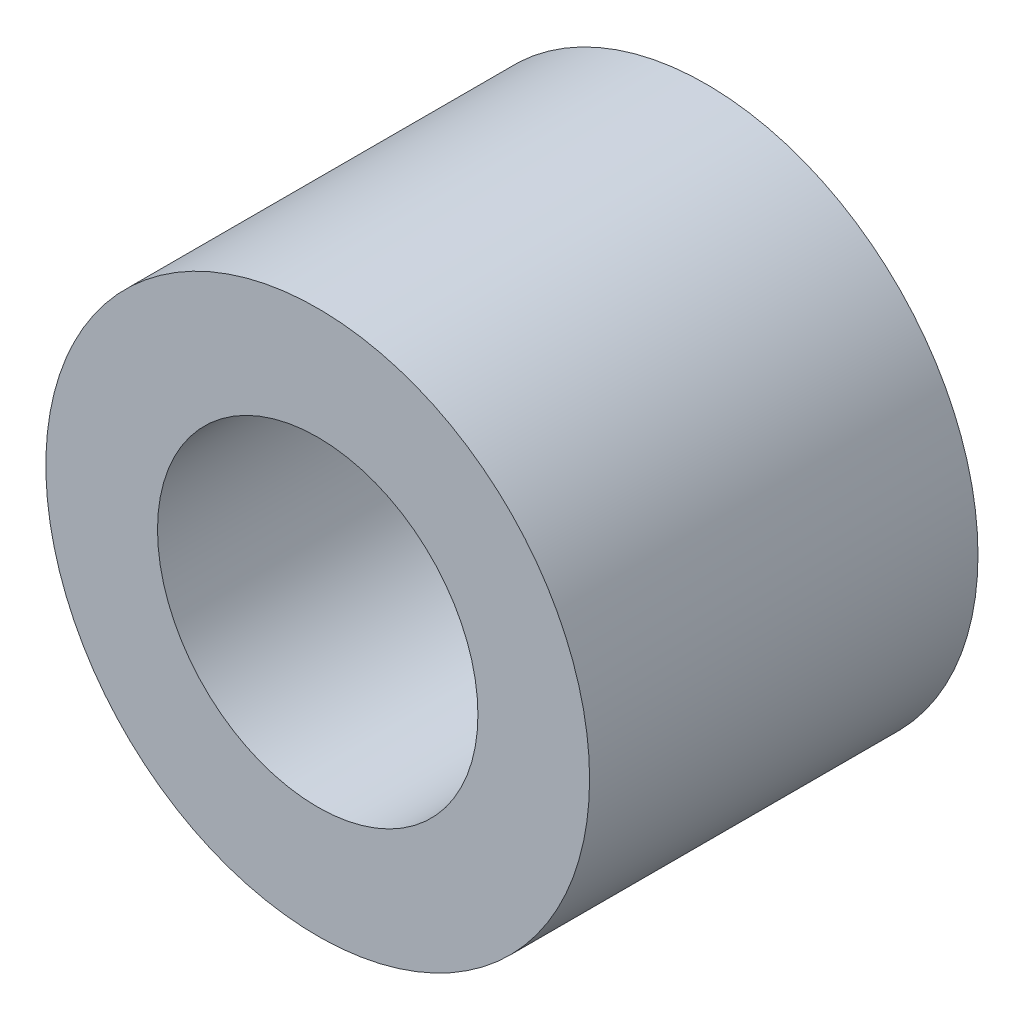
SolidWorks part; units mm, degrees
ref_plane "前视基准面" through (0, 0, 0) normal (0, 0, 1) x (1, 0, 0)
ref_plane "上视基准面" through (0, 0, 0) normal (0, 1, 0) x (1, 0, 0)
ref_plane "右视基准面" through (0, 0, 0) normal (1, 0, 0) x (0, 0, -1)
sketch "草图1" plane through (0, 0, 0) normal (0, 0, 1) x (1, 0, 0)
  circle A0 centre (0, 0) radius 1.65
  circle A1 centre (0, 0) radius 2.8
extrude "凸台-拉伸1" add sketch "草图1" along normal blind 4
